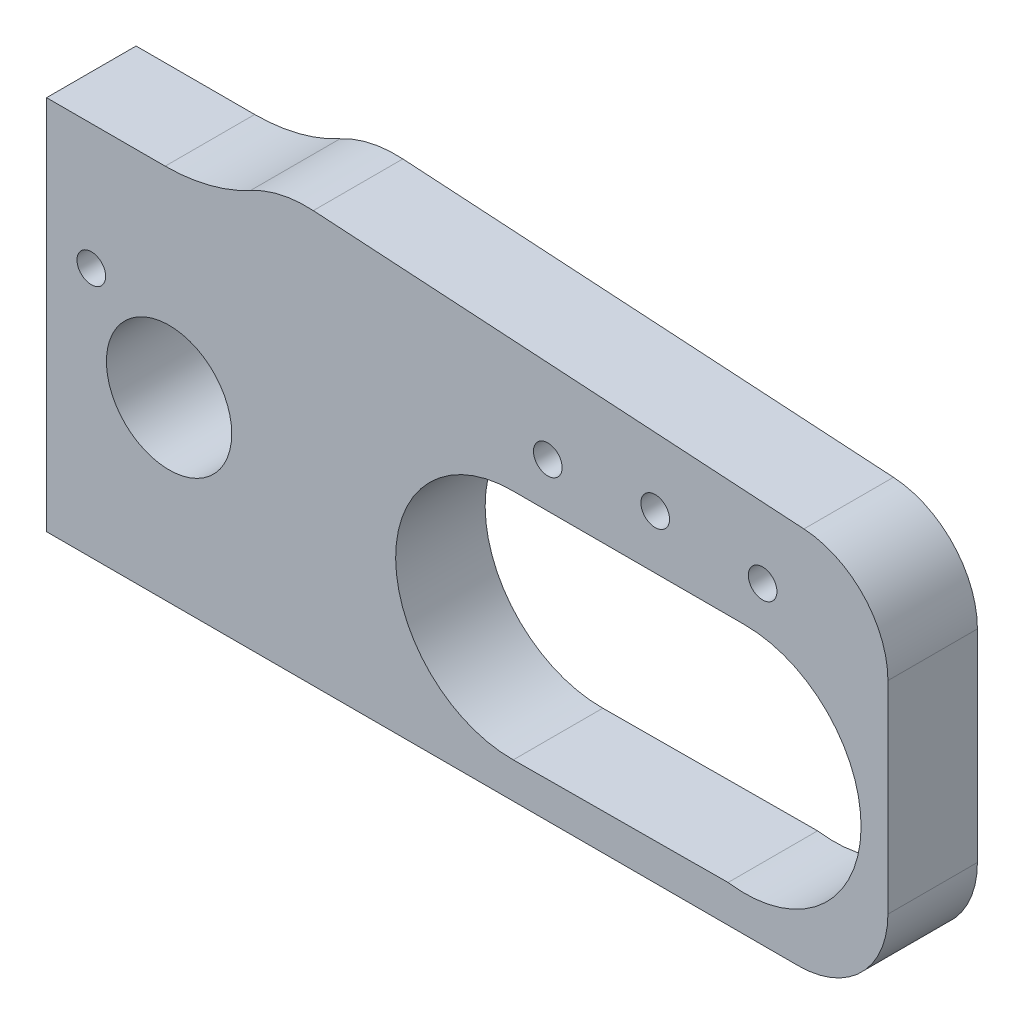
SolidWorks part; units mm, degrees
ref_plane "Front Plane" through (0, 0, 0) normal (1, 0, 0) x (0, 1, 0)
ref_plane "Top Plane" through (0, 0, 0) normal (0, 0, 1) x (0, 1, 0)
ref_plane "Right Plane" through (0, 0, 0) normal (0, 1, 0) x (-1, 0, 0)
sketch "Sketch1" plane through (0, 0, 0) normal (0, 0, 1) x (0, 1, 0)
  line L0 (12.9142, -18.3709) -> (14.6113, 9.0364)
  line L1 (7.9237, -23.0618) -> (-3.3763, -23.0618)
  line L4 (-8.3763, 23.9382) -> (12.6237, 23.9382)
  line L5 (12.6237, 23.9382) -> (12.6237, 17.3122)
  line L7 (-6.3763, -2.0618) -> (-6.2989, -16.0618)
  line L8 (6.6237, -15.0618) -> (6.6237, -2.0618)
  line L10 (-8.3763, 23.9382) -> (-8.3763, -18.0618)
  arc A2 (14.6113, 9.0364) -> (13.8358, 12.54) centre (8.1237, 9.4382) ccw
  arc A3 (12.6237, 17.3122) -> (13.8358, 12.54) centre (22.6237, 17.3122) ccw
  arc A4 (-8.3763, -18.0618) -> (-3.3763, -23.0618) centre (-3.3763, -18.0618) ccw
  arc A5 (7.9237, -23.0618) -> (12.9142, -18.3709) centre (7.9237, -18.0618) ccw
  circle A8 centre (5.6237, 21.4382) radius 0.8
  circle A9 centre (9.1237, -4.0618) radius 0.8
  circle A10 centre (9.6237, -10.0618) radius 0.8
  circle A11 centre (9.1237, -16.0618) radius 0.8
  arc A12 (6.6237, -2.0618) -> (-6.3759, -2.1337) centre (0.1237, -2.0618) ccw
  arc A13 (-6.3096, -14.1329) -> (6.6237, -15.0618) centre (0.1237, -15.0618) ccw
  circle A16 centre (8.1237, 9.4382) radius 5.1
  circle A18 centre (8.1237, 9.4382) radius 5.1
  circle A23 centre (1.537, 17.0949) radius 3.5
  dimension "D8" = 2.5
  dimension "D9" = 1.6
  dimension "D10" = 1.6
  dimension "D11" = 7
  dimension "D1" = 21
  dimension "D2" = 42
  dimension "D3" = 27.4598
  dimension "D4" = 11.3
  dimension "D5" = 2.5
  dimension "D6" = 2.5
  dimension "D7" = 3
extrude "Boss-Extrude1" add sketch "Sketch1" along normal blind 5 contours L1 A5 L0 A2 A3 L5 L4 L10 A4 A13 L7 A12 L8 A11 A10 A9 A8 region at (21.3237, 10.9899, 0)
sketch "Sketch2" plane through (-23.9382, 0, 0) normal (-1, 0, 0) x (0, -1, 0)
  line L0 (-12.6237, 2.5) -> (-9.6237, 2.5) construction
  line L1 (-12.6237, 5) -> (-12.6237, 0) construction
  line L2 (8.3763, 5) -> (8.3763, 0) construction
  circle A0 centre (-9.6237, 2.5) radius 1.25
  circle A1 centre (2.8763, 2.5) radius 1.25
  dimension "D2" = 5.5
  dimension "D3" = 2.5
  dimension "D4" = 2.5
  dimension "D1" = 3
  dimension "D5" = 0
extrude "Cut-Extrude1" cut sketch "Sketch2" against normal blind 5
sketch "Sketch21" plane through (0, 0, 5) normal (0, 0, 1) x (1, 0, 0)
  circle A0 centre (-9.4382, 8.1237) radius 5.1
extrude "Boss-Extrude2" add sketch "Sketch21" against normal blind 1
